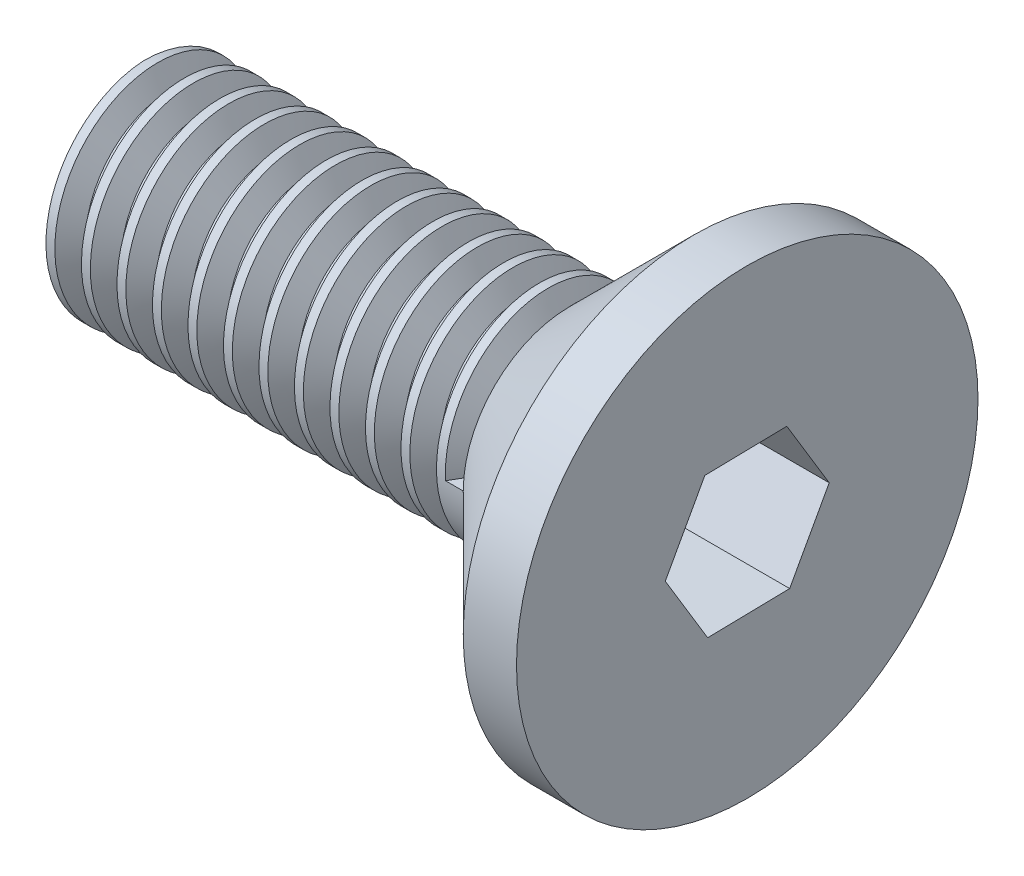
SolidWorks part; units mm, degrees
material "AISI 1020"
ref_plane "Plano superior" through (0, 0, 0) normal (0, 0, 1) x (1, 0, 0)
ref_plane "Plano frontal" through (0, 0, 0) normal (0, 1, 0) x (1, 0, 0)
ref_plane "Plano direito" through (0, 0, 0) normal (1, 0, 0) x (0, 0, -1)
sketch "Esboço1" plane through (0, 0, 0) normal (0, 1, 0) x (1, 0, 0)
  line L0 (0, 0) -> (0, 3)
  line L1 (0, 3) -> (13, 3)
  line L2 (13, 3) -> (16.5, 6.5)
  line L3 (16.5, 6.5) -> (18, 6.5)
  line L4 (18, 6.5) -> (18, 0)
  line L5 (18, 0) -> (0, 0)
  dimension "D1" = 6.5
  dimension "D2" = 45
  dimension "D3" = 1.5
  dimension "D4" = 13
  dimension "D5" = 3
revolve "Revolução1" add sketch "Esboço1" angle 360 about L5
sketch "Esboço2" plane through (18, 0, 0) normal (1, 0, 0) x (0, 0, -1)
  line L2 (-1.1947, 1.9764) -> (-2.3089, -0.0464)
  line L3 (-2.3089, -0.0464) -> (-1.1143, -2.0228)
  line L4 (-1.1143, -2.0228) -> (1.1947, -1.9764)
  line L5 (1.1947, -1.9764) -> (2.3089, 0.0464)
  line L6 (2.3089, 0.0464) -> (1.1143, 2.0228)
  line L7 (1.1143, 2.0228) -> (-1.1947, 1.9764)
  circle A0 centre (0, 0) radius 2 construction
  dimension "D1" = 4
extrude "Corte-extrusão1" cut sketch "Esboço2" against normal blind 4
thread "Rosca1" pitch 1 method cut profile "Perfil da rosca1" start angle 0, offset 0, length 0, pitch 1, diameter 6
ref_plane "Plano1" through (0, 0, -3) normal (0, 1, 0) x (0, 0, 1)
sketch "Perfil da rosca1" plane through (0, 0, -3) normal (0, 1, 0) x (0, 0, 1)
  line L0 (0, 0) -> (0, 1) construction
  line L1 (0, 0) -> (0.5413, 0.3125)
  line L2 (0.5413, 0.3125) -> (0.5413, 0.4375)
  line L3 (0.5413, 0.4375) -> (0, 0.75)
  line L4 (0.5413, 0.375) -> (0, 0.375) construction
  line L11 (0, 0) -> (0, 0.75)
  point P2 (0, 0)
  dimension "Pitch" = 1
  dimension "Profile_Angle" = 60
  dimension "Profile_Land" = 0.125
  dimension "Profile_Height" = 0.5413
sketch "Esboço22" plane through (0, 0, 0) normal (-1, 0, 0) x (0, 0, 1)
  circle A0 centre (0, 0) radius 3
extrude "Corte-extrusão2" cut sketch "Esboço22" against normal blind 1
